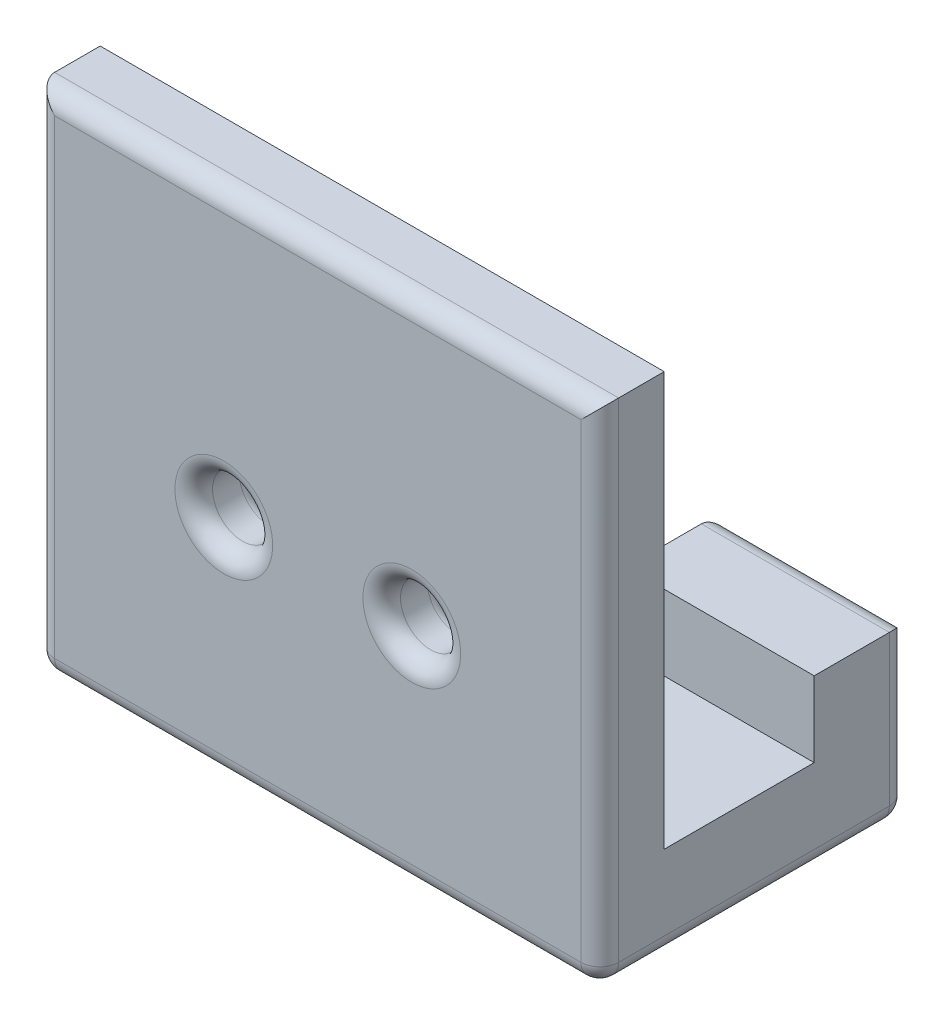
SolidWorks part; units mm, degrees
note: The reader was unsure of these and kept them because the rebuilt part matched: shared geometry of "Sketch1<3>".
ref_plane "Front Plane" through (0, 0, 0) normal (0, 0, 1) x (1, 0, 0)
ref_plane "Top Plane" through (0, 0, 0) normal (0, 1, 0) x (1, 0, 0)
ref_plane "Right Plane" through (0, 0, 0) normal (1, 0, 0) x (0, 0, -1)
sketch "Sketch1" plane through (0, 0, 0) normal (0, 1, 0) x (1, 0, 0)
  line L0 (-44.6146, -35.1232) -> (-14.6146, -35.1232)
  line L1 (-44.6146, -25.9209) -> (-14.6146, -25.9209)
  line L2 (-24.6146, -23.7209) -> (-14.6146, -23.7209)
  line L3 (-44.6146, -23.7209) -> (-34.6146, -23.7209)
  line L4 (-34.6146, -25.9209) -> (-34.6146, -18.7209)
  line L5 (-44.6146, -18.7209) -> (-34.6146, -18.7209)
  line L6 (-44.6146, -18.7209) -> (-44.6146, -35.1232)
  line L7 (-14.6146, -18.7209) -> (-14.6146, -35.1232)
  line L12 (-24.6146, -25.9209) -> (-24.6146, -18.7209)
  line L13 (-14.6146, -18.7209) -> (-24.6146, -18.7209)
extrude "Boss-Extrude1" add sketch "Sketch1" along normal blind 5
extrude "Boss-Extrude2" add sketch "Sketch1<3>" along normal blind 9
sketch "Sketch1<3>" plane through (0, 0, 0) normal (0, 1, 0) x (1, 0, 0) same geometry as "Sketch1"
sketch "Sketch3" plane through (0, 5, 0) normal (0, 1, 0) x (1, 0, 0)
  line L0 (-44.6146, -31.6985) -> (-44.6146, -35.1232)
  line L2 (-34.6146, -31.6985) -> (-14.6146, -31.6985)
  line L3 (-44.6146, -35.1232) -> (-14.6146, -35.1232)
  line L4 (-14.6146, -35.1232) -> (-14.6146, -31.6985)
  line L5 (-14.6146, -23.7209) -> (-14.6146, -35.1232) construction
  line L10 (-44.6146, -31.6985) -> (-14.6146, -31.6985)
  line L11 (-44.6146, -23.7209) -> (-44.6146, -35.1232) construction
extrude "Boss-Extrude3" add sketch "Sketch3" along normal blind 22
sketch "Sketch4" plane through (0, 0, 31.6985) normal (0, 0, -1) x (-1, 0, 0)
  circle A0 centre (34.6146, 12) radius 1.6
  circle A1 centre (24.6146, 12) radius 1.6
extrude "Cut-Extrude1" cut sketch "Sketch4" against normal up to surface (3.4247 mm away) up to face at (-29.6146, 13.5, 35.1232)
fillet "Fillet1" radius 1 4 edges at (-26.2146, 12, 31.6985) (-36.2146, 12, 31.6985) (-26.2146, 12, 35.1232) (-36.2146, 12, 35.1232)
fillet "Fillet2" radius 1 17 edges at (-44.6146, 13.5, 35.1232) (-29.6146, 27, 35.1232) (-14.6146, 13.5, 35.1232) (-14.6146, 4.5, 18.7209) (-19.6146, 9, 18.7209) (-24.6146, 4.5, 18.7209) (-34.6146, 4.5, 18.7209) (-39.6146, 9, 18.7209) (-44.6146, 4.5, 18.7209) (-29.6146, 0, 25.9209) (-34.6146, 0, 22.3209) (-39.6146, 0, 18.7209) (-44.6146, 0, 26.9221) (-29.6146, 0, 35.1232) (-14.6146, 0, 26.9221) (-19.6146, 0, 18.7209) (-24.6146, 0, 22.3209)
